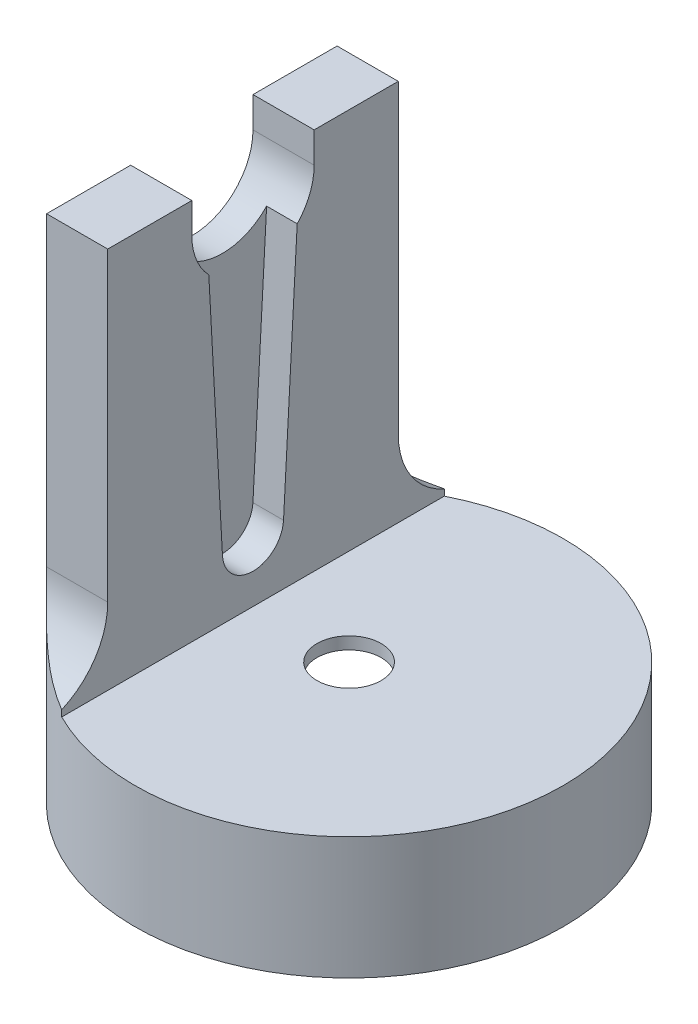
SolidWorks part; units mm, degrees
ref_plane "Front Plane" through (0, 0, 0) normal (0, 0, 1) x (1, 0, 0)
ref_plane "Top Plane" through (0, 0, 0) normal (0, 1, 0) x (1, 0, 0)
ref_plane "Right Plane" through (0, 0, 0) normal (1, 0, 0) x (0, 0, -1)
sketch "Sketch1" plane through (0, 0, 0) normal (0, 1, 0) x (1, 0, 0)
  circle A0 centre (0, 0) radius 14
  dimension "D1" = 28
extrude "Boss-Extrude1" add sketch "Sketch1" against normal blind 8
shell "Shell1" thickness 0.8 removed face at (0, -8, 14)
sketch "Sketch2" plane through (0, 0, 0) normal (0, 1, 0) x (1, 0, 0)
  circle A0 centre (0, 0) radius 2.1
  dimension "D1" = 4.2
extrude "Cut-Extrude1" cut sketch "Sketch2" against normal blind 2
sketch "Sketch3" plane through (0, 0, 0) normal (0, 1, 0) x (1, 0, 0)
  line L0 (0, 0) -> (7.5733, 0) construction
  line L1 (-10.2835, 9.5) -> (-6.2835, 9.5)
  line L2 (-10.2835, 9.5) -> (-10.2835, -9.5)
  line L3 (-10.2835, -9.5) -> (-6.2835, -9.5)
  line L4 (-6.2835, 9.5) -> (-6.2835, -9.5)
  circle A0 centre (0, 0) radius 14 construction
  dimension "D1" = 19
  dimension "D2" = 4
extrude "Boss-Extrude2" add sketch "Sketch3" along normal blind 25
sketch "Sketch4" plane through (-6.2835, 0, 0) normal (1, 0, 0) x (0, 0, -1)
  line L0 (-9.5, 25) -> (9.5, 25) construction
  line L1 (-2.8908, 20.2353) -> (-1.997, 3.8908)
  line L2 (2.8908, 20.2353) -> (1.997, 3.8908)
  line L3 (0, 23) -> (0, 17.0634) construction
  line L4 (-4, 23) -> (-4, 25)
  line L5 (4, 23) -> (4, 25)
  line L6 (-4, 25) -> (4, 25)
  arc A0 (-4, 23) -> (4, 23) centre (0, 23) ccw
  circle A1 centre (0, 4) radius 2
  point P5 (0, 25)
  dimension "D1" = 19
  dimension "D2" = 8
  dimension "D3" = 4
  dimension "D4" = 2
  dimension "D5" = 6.26
extrude "Cut-Extrude2" cut sketch "Sketch4" against normal blind 19 contours A0 region at (-6.2835, 22.3517, 0)
extrude "Cut-Extrude3" cut sketch "Sketch4<3>" against normal blind 2 contours A1 L2 A0 L1 | A1 region at (-6.2835, 12.8081, 0) region at (-6.2835, 4, 0)
sketch "Sketch4<3>" plane through (-6.2835, 0, 0) normal (1, 0, 0) x (0, 0, -1) same geometry as "Sketch4"
fillet "Fillet1" radius 5 1 edges at (-10.2835, 0, 0)
fillet "Fillet2" radius 5 2 edges at (-8.2835, 0, -9.5) (-8.2835, 0, 9.5)
sketch "Sketch5" plane through (0, 0, 0) normal (0, 0, 1) x (1, 0, 0)
  line L0 (-2, -3) -> (-2, -8)
  line L1 (-14, -8) -> (14, -8) construction
  line L2 (2, -3) -> (2, -8)
  line L3 (-2, -8) -> (2, -8)
  arc A0 (2, -3) -> (-2, -3) centre (0, -3) ccw
  point P2 (0, -1)
  dimension "D2" = 4
  dimension "D1" = 1
extrude "Cut-Extrude4" cut sketch "Sketch5" against normal blind 20
